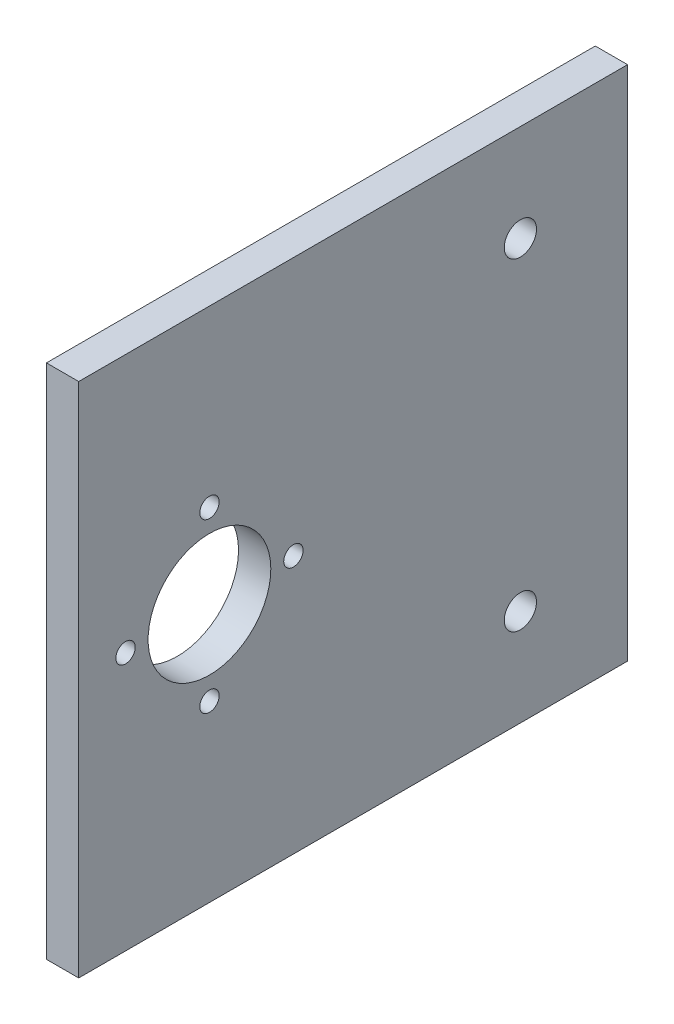
SolidWorks part; units mm, degrees
ref_plane "Front Plane" through (0, 0, 0) normal (1, 0, 0) x (0, 1, 0)
ref_plane "Top Plane" through (0, 0, 0) normal (0, 0, 1) x (0, 1, 0)
ref_plane "Right Plane" through (0, 0, 0) normal (0, 1, 0) x (-1, 0, 0)
sketch "Sketch1" plane through (0, 0, 0) normal (1, 0, 0) x (0, 1, 0)
  line L0 (0, 42.5) -> (0, -42.5) construction
  line L1 (-40, -42.5) -> (40, -42.5)
  line L2 (-40, -42.5) -> (-40, 42.5)
  line L3 (-40, 42.5) -> (40, 42.5)
  line L4 (40, -42.5) -> (40, 42.5)
  line L5 (-40, -42.5) -> (40, 42.5) construction
  line L6 (-40, 42.5) -> (40, -42.5) construction
  line L7 (-40, 22.25) -> (40, 22.25) construction
  line L9 (-25, -25.9) -> (25, -25.9) construction
  line L10 (-25, -25.9) -> (-25, 25.9) construction
  line L11 (-25, 25.9) -> (25, 25.9) construction
  line L12 (25, -25.9) -> (25, 25.9) construction
  line L13 (-25, -25.9) -> (25, 25.9) construction
  line L14 (-25, 25.9) -> (25, -25.9) construction
  circle A1 centre (0, 35.25) radius 1.5
  circle A2 centre (0, 9.25) radius 1.5
  circle A3 centre (-13, 22.25) radius 1.5
  circle A4 centre (13, 22.25) radius 1.5
  circle A5 centre (0, 22.25) radius 9.5
  circle A6 centre (-25, -25.9) radius 2.5
  circle A7 centre (25, -25.9) radius 2.5
  point P0 (0, 0)
  point P20 (0, 0)
  dimension "D5" = 3
  dimension "D6" = 3
  dimension "D7" = 13
  dimension "D8" = 19
  dimension "D11" = 5
  dimension "D12" = 5
  dimension "D1" = 80
  dimension "D2" = 85
  dimension "D3" = 64.75
  dimension "D4" = 13
  dimension "D9" = 16.6
  dimension "D10" = 50
extrude "Boss-Extrude1" add sketch "Sketch1" along normal blind 5
